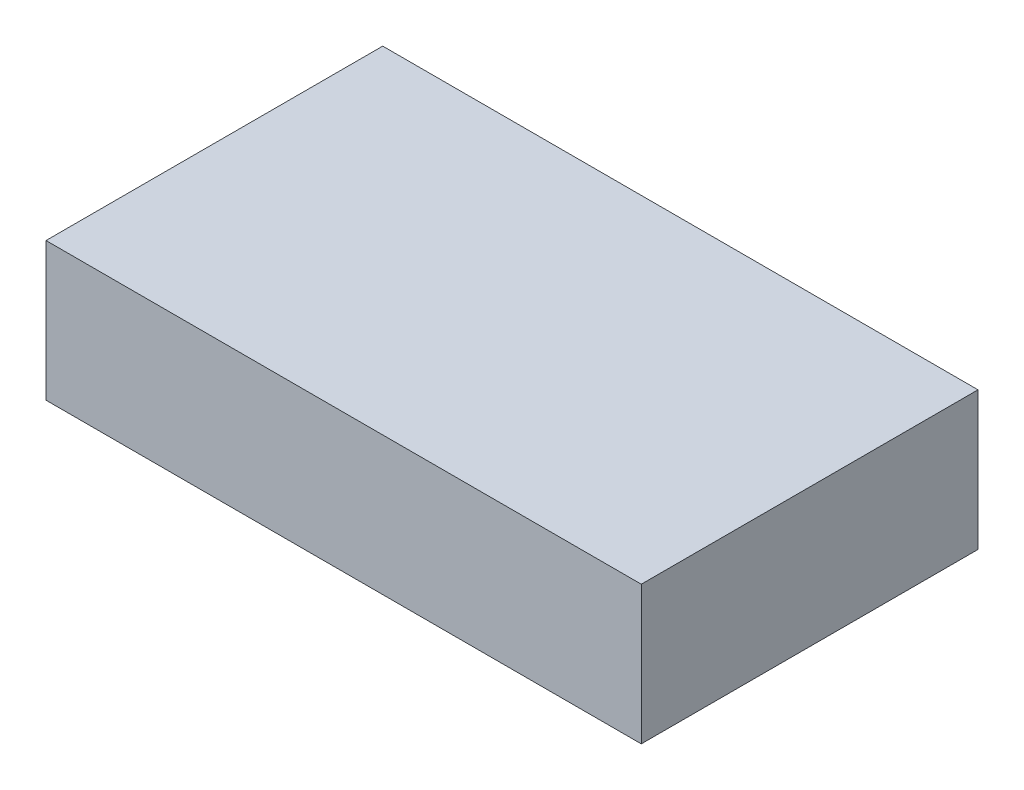
SolidWorks part; units mm, degrees
ref_plane "Front Plane" through (0, 0, 0) normal (0, 0, 1) x (1, 0, 0)
ref_plane "Top Plane" through (0, 0, 0) normal (0, 1, 0) x (1, 0, 0)
ref_plane "Right Plane" through (0, 0, 0) normal (1, 0, 0) x (0, 0, -1)
sketch "Sketch1" plane through (0, 0, 0) normal (0, 1, 0) x (1, 0, 0)
  line L1 (49.5, -28) -> (-49.5, -28)
  line L2 (49.5, -28) -> (49.5, 28)
  line L3 (49.5, 28) -> (-49.5, 28)
  line L4 (-49.5, -28) -> (-49.5, 28)
  line L5 (49.5, -28) -> (-49.5, 28) construction
  line L6 (49.5, 28) -> (-49.5, -28) construction
  point P0 (0, 0)
  dimension "D1" = 56
  dimension "D2" = 99
extrude "Boss-Extrude1" add sketch "Sketch1" along normal blind 23
